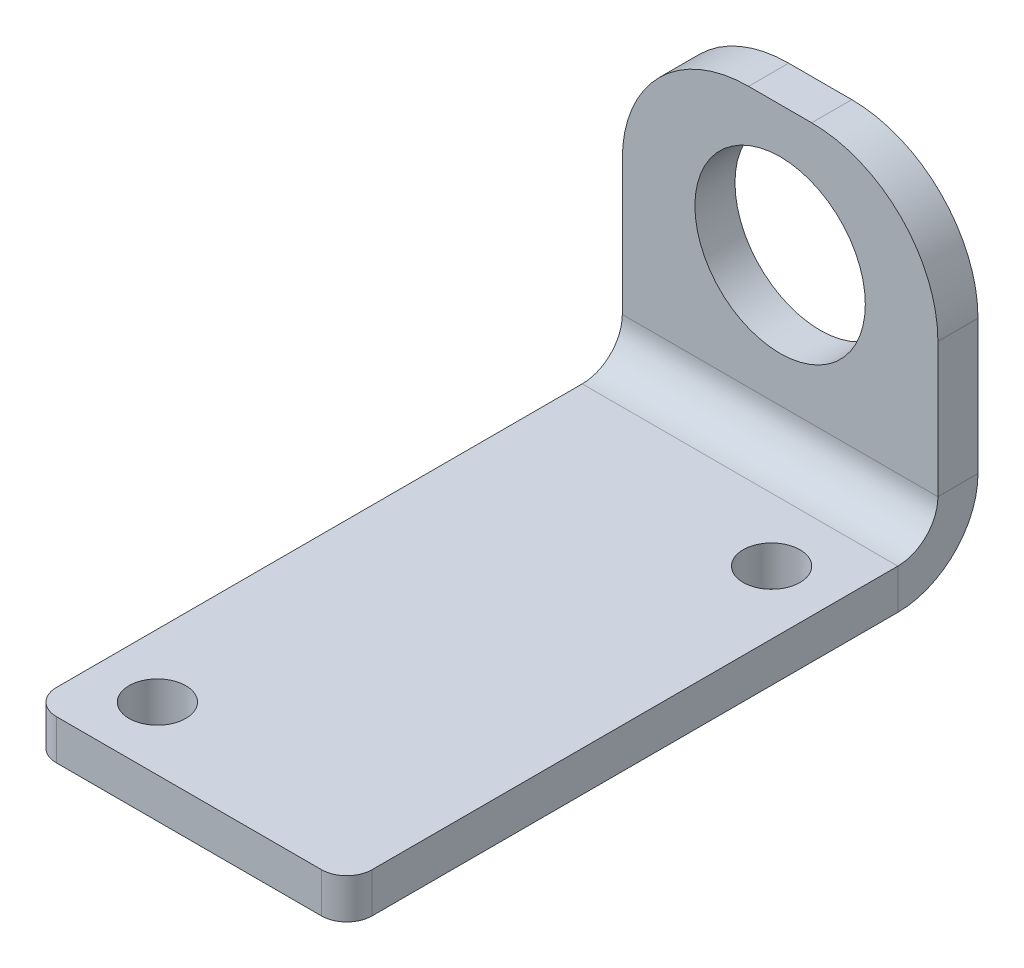
SolidWorks part; units mm, degrees
note: The reader was unsure of these and kept them because the rebuilt part matched: flange length of "Edge-Flange1".
material "6061-T6 (SS)"
ref_plane "Front Plane" through (0, 0, 0) normal (0, 0, 1) x (1, 0, 0)
ref_plane "Top Plane" through (0, 0, 0) normal (0, 1, 0) x (1, 0, 0)
ref_plane "Right Plane" through (0, 0, 0) normal (1, 0, 0) x (0, 0, -1)
sketch "Sketch1" plane through (0, 0, 0) normal (0, 1, 0) x (1, 0, 0)
  line L1 (-12.5, 0) -> (12.5, 0)
  line L2 (-12.5, 0) -> (-12.5, 50)
  line L3 (-12.5, 50) -> (12.5, 50)
  line L4 (12.5, 0) -> (12.5, 50)
  point P4 (0, 0)
  dimension "D1" = 25
  dimension "D2" = 50
base flange "Base-Flange1" sketch "Sketch1" thickness 3.175 reverse thickness direction no parameters "D1"=3.175
edge flange "Edge-Flange1" sketch "Sketch8" flange angle 90 flange length 27 flange position material inside bend radius 3.175 thickness 3.175 relief rectangular parameters "D6"=10
sketch "Sketch8" plane through (0, 0, -50) normal (0, 0, -1) x (-1, 0, 0)
  line L2 (-12.5, 0) -> (-12.5, 23.825)
  line L3 (-12.5, 23.825) -> (12.5, 23.825)
  line L4 (12.5, 23.825) -> (12.5, 0)
  line L7 (-12.5, 0) -> (12.5, 0) construction
  line L8 (-12.5, 0) -> (12.5, 0)
bend "EdgeBend1" bend radius 3.175 bend angle 90 parameters "D5"=1
sketch "Sketch9" plane through (0, 0, -50) normal (0, 0, -1) x (-1, 0, 0)
  line L1 (12.5, 3.175) -> (12.5, 23.825) construction
  line L2 (12.5, 23.825) -> (-12.5, 23.825) construction
  point P0 (0, 13.5)
  point P6 (12.5, 13.5)
  point P9 (0, 23.825)
hole_wizard "M12 Clearance Hole1" positions "Sketch11" profile "Sketch13" hole size "M12" standard "ANSI Metric" end condition through all
sketch "Sketch11" plane through (0, 0, -50) normal (0, 0, -1) x (-1, 0, 0)
  point P0 (0, 13.5)
sketch "Sketch13" plane through (0, 13.5, -50) normal (1, 0, 0) x (0, 1, 0)
  line L0 (0, 0) -> (0, 50)
  line L1 (0, 50) -> (6.75, 50)
  line L2 (6.75, 50) -> (6.75, 0)
  line L5 (6.75, 0) -> (0, 0)
  line L11 (0, -6.35) -> (0, 107.95) construction
  dimension "Thru Hole Dia." = 13.5
  dimension "Thru Hole Depth" = 50
sketch "Sketch15" plane through (0, 0, 0) normal (0, 1, 0) x (1, 0, 0)
  line L0 (-7.5, 5) -> (7.5, 38.65) construction
  line L1 (-12.5, 43.65) -> (-12.5, 0) construction
  line L2 (12.5, 0) -> (12.5, 43.65) construction
  line L3 (-12.5, 43.65) -> (12.5, 43.65) construction
  line L4 (-12.5, 0) -> (12.5, 0) construction
  point P0 (-7.5, 5)
  point P1 (7.5, 38.65)
  dimension "D1" = 5
  dimension "D2" = 5
  dimension "D3" = 5
  dimension "D4" = 5
hole_wizard "M4 Clearance Hole1" positions "Sketch16" profile "Sketch18" hole size "M4" standard "ANSI Metric" end condition through all
sketch "Sketch16" plane through (0, 0, 0) normal (0, 1, 0) x (1, 0, 0)
  point P0 (-7.5, 5)
  point P3 (7.5, 38.65)
sketch "Sketch18" plane through (-7.5, 0, -5) normal (1, 0, 0) x (0, 0, 1)
  line L0 (0, 0) -> (0, 3.175)
  line L1 (0, 3.175) -> (2.25, 3.175)
  line L2 (2.25, 3.175) -> (2.25, 0)
  line L5 (2.25, 0) -> (0, 0)
  line L11 (0, -6.35) -> (0, 107.95) construction
  dimension "Thru Hole Dia." = 4.5
  dimension "Thru Hole Depth" = 3.175
fillet "Fillet1" radius 10 2 edges at (-12.5, 23.825, -48.4125) (12.5, 23.825, -48.4125)
fillet "Fillet2" radius 2 2 edges at (12.5, -1.5875, 0) (-12.5, -1.5875, 0)
sketch "Bend-Lines1" [suppressed] plane through (0, 0, 0) normal (0, 1, 0) x (1, 0, 0)
sketch "Bounding-Box1" [suppressed] plane through (0, 0, 0) normal (0, 1, 0) x (1, 0, 0)
sheet metal parameters "Sheet-Metal1" thickness 3.175 parameters "D1"=3.175
flat pattern "Flat-Pattern1" [suppressed]
sketch "Bend-Lines2" plane through (0, 0, 0) normal (0, 1, 0) x (1, 0, 0)
sketch3d "Bounding-Box2" [suppressed]
  line L0 (20, 0, 0) -> (20, 50, 0) construction
  line L1 (-20, 0, 0) -> (-20, 50, 0) construction
  line L2 (20, 0, 0) -> (-20, 0, 0) construction
  line L3 (20, 50, 0) -> (-20, 50, 0) construction
sheet metal parameters "Sheet-Metal2" thickness 3.175 parameters "D1"=3.175
flat pattern "Flat-Pattern1"
sketch "Bend-Lines2" plane through (0, 0, 0) normal (0, 1, 0) x (1, 0, 0)
  line L0 (10, 47.3905) -> (-10, 47.3905) construction
  line L1 (10, 47.3905) -> (-10, 47.3905) construction
sketch3d "Bounding-Box2" [suppressed]
  line L0 (-10, 0, 0) -> (-10, 74.7809, 0) construction
  line L1 (10, 0, 0) -> (10, 74.7809, 0) construction
  line L2 (-10, 0, 0) -> (10, 0, 0) construction
  line L3 (-10, 74.7809, 0) -> (10, 74.7809, 0) construction
bend of the flat pattern "Flatten-<EdgeBend1>1"
sheet metal parameters "Sheet-Metal3" thickness 3.175 parameters "D1"=3.175
flat pattern "Flat-Pattern1" [suppressed]
sketch "Bend-Lines2" plane through (0, 0, 0) normal (0, 1, 0) x (1, 0, 0)
  line L0 (10, 47.3905) -> (-10, 47.3905) construction
  line L1 (10, 47.3905) -> (-10, 47.3905) construction
sketch3d "Bounding-Box2" [suppressed]
  line L0 (-10, 0, 0) -> (-10, 74.7809, 0) construction
  line L1 (10, 0, 0) -> (10, 74.7809, 0) construction
  line L2 (-10, 0, 0) -> (10, 0, 0) construction
  line L3 (-10, 74.7809, 0) -> (10, 74.7809, 0) construction
bend of the flat pattern "Flatten-<EdgeBend1>1"
sketch "Sketch9-1" [suppressed] plane through (0, -3.175, -47.9559) normal (0, -1, 0) x (-1, 0, 0)
  point P0 (0, 15)
sheet metal parameters "Sheet-Metal4" thickness 3.175 parameters "D1"=3.175
flat pattern "Flat-Pattern1" [suppressed]
sketch "Bend-Lines2" plane through (0, 0, 0) normal (0, 1, 0) x (1, 0, 0)
  line L0 (12.5, 47.3905) -> (-12.5, 47.3905) construction
  line L1 (12.5, 47.3905) -> (-12.5, 47.3905) construction
sketch3d "Bounding-Box2" [suppressed]
  line L0 (12.5, 0, 0) -> (12.5, 71.7809, 0) construction
  line L1 (-12.5, 0, 0) -> (-12.5, 71.7809, 0) construction
  line L2 (12.5, 0, 0) -> (-12.5, 0, 0) construction
  line L3 (12.5, 71.7809, 0) -> (-12.5, 71.7809, 0) construction
bend of the flat pattern "Flatten-<EdgeBend1>1"
sketch "Sketch9-2" plane through (0, -3.175, -47.9559) normal (0, -1, 0) x (-1, 0, 0)
  point P0 (0, 13.5)
equation "\"D4@Sketch15\"=\"D3@Sketch15\""
equation "\"D1@Sketch15\"=\"D4@Sketch15\""
equation "\"D2@Sketch15\"=\"D1@Sketch15\""
